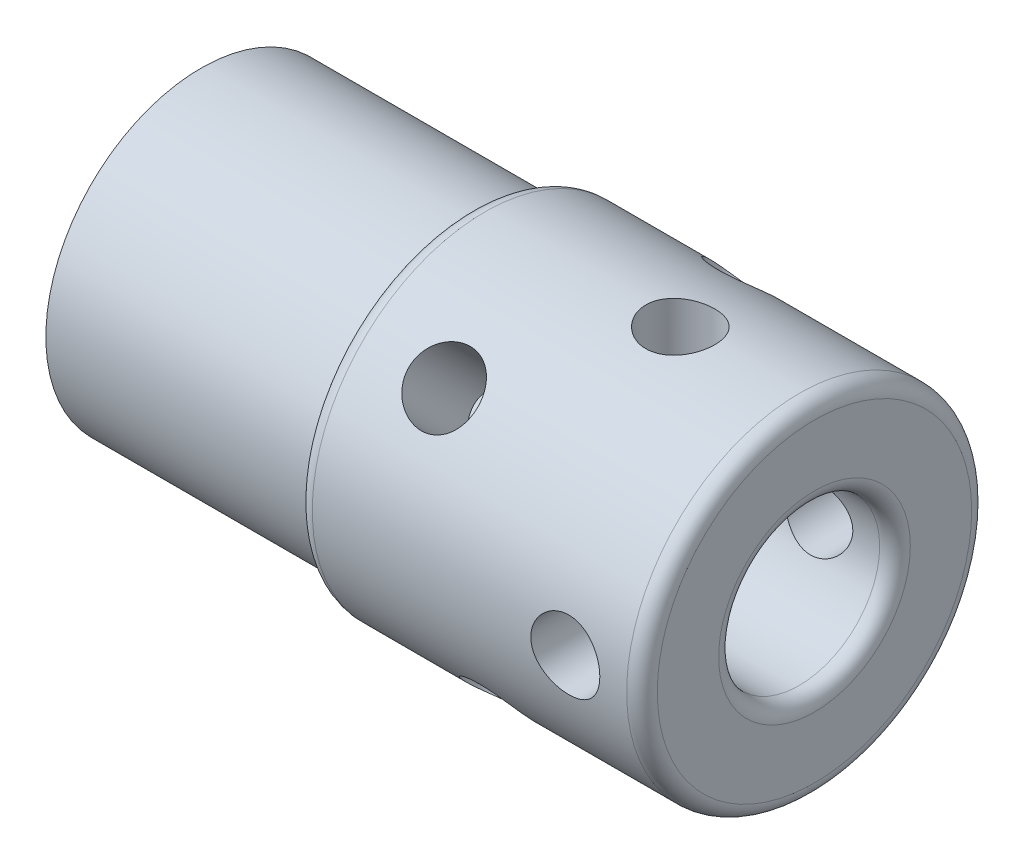
SolidWorks part; units mm, degrees
ref_plane "Front Plane" through (0, 0, 0) normal (0, 0, 1) x (1, 0, 0)
ref_plane "Top Plane" through (0, 0, 0) normal (0, 1, 0) x (1, 0, 0)
ref_plane "Right Plane" through (0, 0, 0) normal (1, 0, 0) x (0, 0, -1)
sketch "Sketch1" plane through (0, 0, 0) normal (1, 0, 0) x (0, 0, -1)
  circle A0 centre (0, 0) radius 4.05
  circle A1 centre (0, 0) radius 2.1
  dimension "D1" = 4.2
  dimension "D2" = 8.1
extrude "Boss-Extrude1" add sketch "Sketch1" along normal blind 7
sketch "Sketch2" plane through (7, 0, 0) normal (1, 0, 0) x (0, 0, -1)
  circle A0 centre (0, 0) radius 2.1
  circle A1 centre (0, 0) radius 4.5
  dimension "D1" = 9
  dimension "D2" = 4.2
extrude "Boss-Extrude2" add sketch "Sketch2" along normal blind 9
fillet "Fillet1" radius 0.4 1 edges at (16, 0, -2.1)
sketch "Sketch3" plane through (0, 0, 0) normal (0, 1, 0) x (1, 0, 0)
  line L0 (16, -4.5) -> (16, 4.5) construction
  circle A0 centre (12.5, 0) radius 0.9
  dimension "D1" = 3.5
  dimension "D2" = 1.8
extrude "Cut-Extrude1" cut sketch "Sketch3" against normal through all both and the other way through all
sketch "Sketch4" plane through (0, 0, 0) normal (0, 0, 1) x (1, 0, 0)
  line L0 (16, -4.5) -> (16, 4.5) construction
  circle A0 centre (14, 0) radius 0.9
  dimension "D1" = 1.8
  dimension "D2" = 2
extrude "Cut-Extrude2" cut sketch "Sketch4" against normal through all both and the other way through all
sketch "Sketch5" plane through (0, 0, 0) normal (0, 1, 0) x (1, 0, 0)
  line L0 (7.404, 4.5) -> (10.9949, 4.5) construction
  line L1 (13.1001, 4.5) -> (7, 4.5) construction
ref_axis "Axis1" through (7.404, 0, -4.5) along (1, 0, 0)
ref_plane "Plane1" through (0, 2.25, -2.25) normal (0, -0.7071, 0.7071) x (1, 0, 0)
sketch "Sketch6" plane through (0, 2.25, -2.25) normal (0, -0.7071, 0.7071) x (1, 0, 0)
  line L0 (16, -4.5) -> (16, 4.5) construction
  circle A0 centre (11, 0) radius 0.9
  dimension "D1" = 1.8
  dimension "D2" = 5
extrude "Cut-Extrude3" cut sketch "Sketch6" against normal through all both and the other way through all
ref_plane "Plane2" through (0, -2.25, -2.25) normal (0, -0.7071, -0.7071) x (1, 0, 0)
sketch "Sketch7" plane through (0, -2.25, -2.25) normal (0, -0.7071, -0.7071) x (1, 0, 0)
  line L0 (16, -4.5) -> (16, 4.5) construction
  circle A0 centre (9.5, 0) radius 0.9
  dimension "D1" = 6.5
  dimension "D2" = 1.8
extrude "Cut-Extrude4" cut sketch "Sketch7" against normal through all both and the other way through all
fillet "Fillet2" radius 0.4 1 edges at (16, 0, -4.5)
fillet "Fillet3" radius 0.4 1 edges at (7, 0, -4.5)
